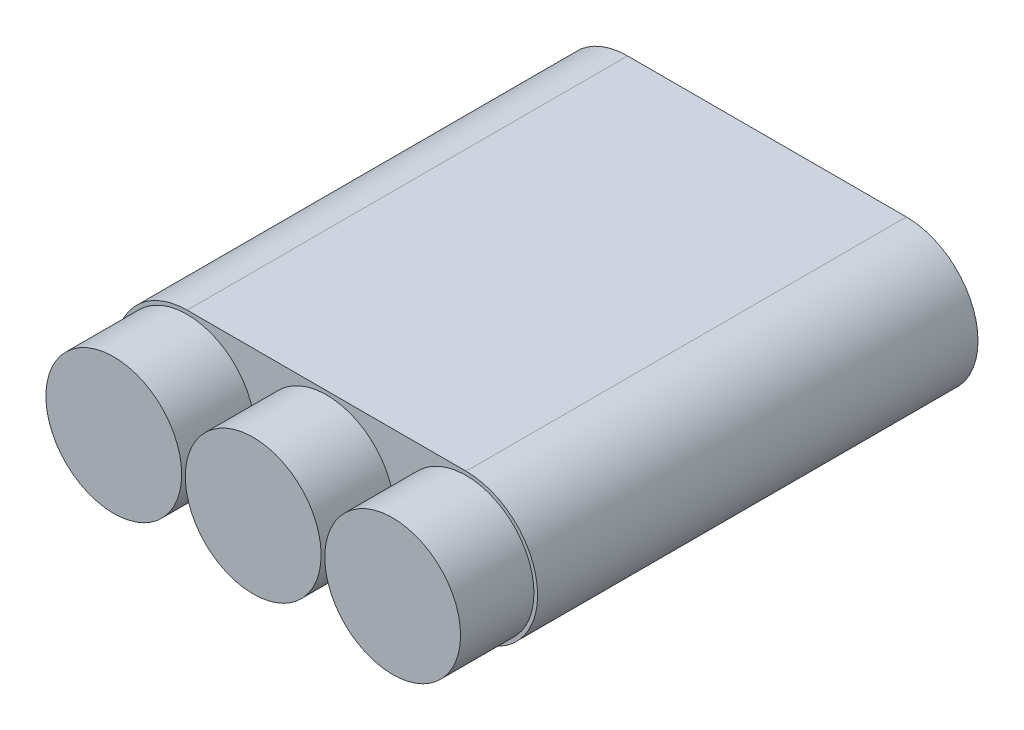
SolidWorks part; units mm, degrees
ref_plane "Ebene vorne" through (0, 0, 0) normal (0, 0, 1) x (1, 0, 0)
ref_plane "Ebene oben" through (0, 0, 0) normal (0, 1, 0) x (1, 0, 0)
ref_plane "Ebene rechts" through (0, 0, 0) normal (1, 0, 0) x (0, 0, -1)
sketch "Skizze1" plane through (0, 0, 0) normal (0, 0, 1) x (1, 0, 0)
  line L0 (-19, 0) -> (19, 0) construction
  line L1 (-19, 0) -> (19, 0) construction
  line L2 (-19, 9.75) -> (19, 9.75)
  line L3 (-19, -9.75) -> (19, -9.75)
  line L4 (19, 9.75) -> (19, 9.25) construction
  line L5 (9.25, 0) -> (9.75, 0) construction
  circle A0 centre (0, 0) radius 9.25
  circle A1 centre (19, 0) radius 9.25
  circle A2 centre (-19, 0) radius 9.25
  arc A3 (-19, 9.75) -> (-19, -9.75) centre (-19, 0) ccw
  arc A4 (19, -9.75) -> (19, 9.75) centre (19, 0) ccw
  point P7 (0, 0)
  dimension "D1" = 18.5
  dimension "D2" = 0.5
  dimension "D3" = 0.5
extrude "Aufsatz-Linear austragen1" add sketch "Skizze1" along normal blind 10 contours A2 | A0 | A1 region at (0, 0, 0) region at (19, 0, 0) region at (-19, 0, 0)
extrude "Aufsatz-Linear austragen7" add sketch "Skizze1<5>" against normal blind 60 contours A2 | A0 | A1 | L3 A4 L2 A3 A0 A1 A2 region at (0, 9.6893, 0) region at (0, 0, 0) region at (19, 0, 0) region at (-19, 0, 0)
sketch "Skizze1<5>" plane through (0, 0, 0) normal (0, 0, 1) x (1, 0, 0) same geometry as "Skizze1"
